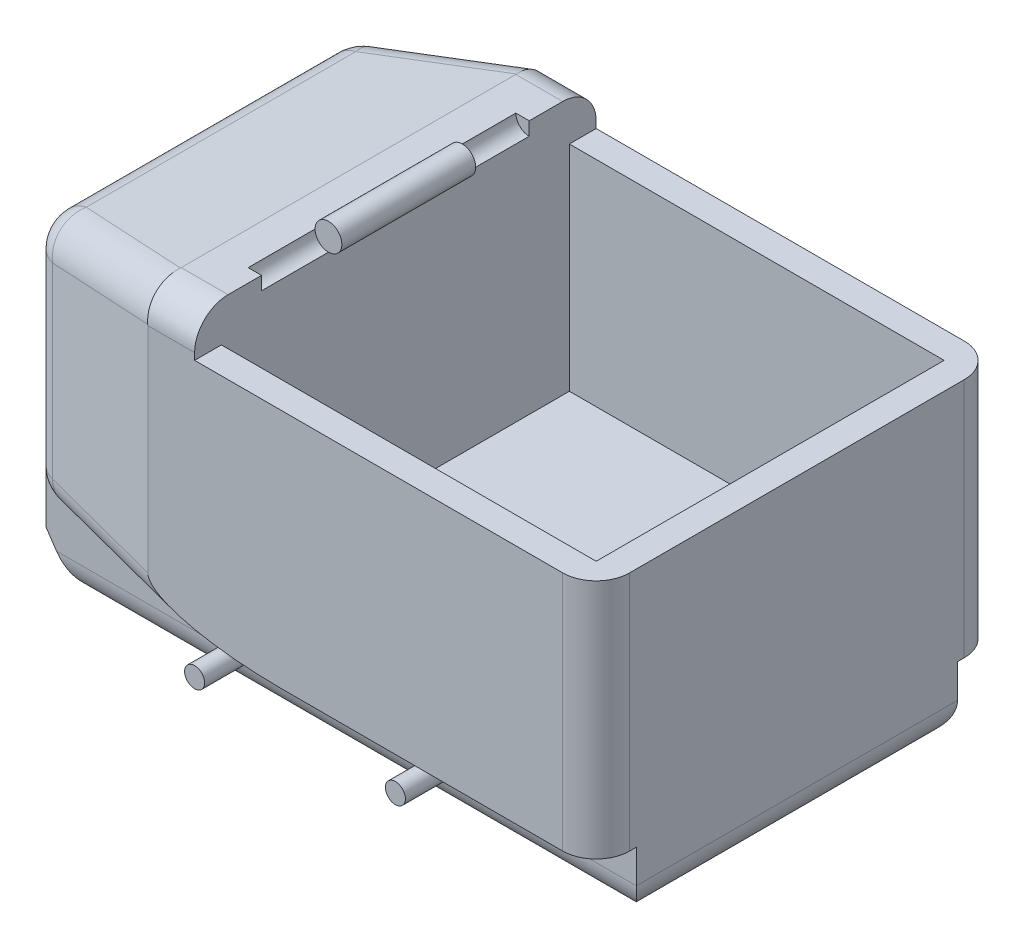
SolidWorks part; units mm, degrees
material "ABS"
ref_plane "Спереди" through (0, 0, 0) normal (0, 0, 1) x (1, 0, 0)
ref_plane "Сверху" through (0, 0, 0) normal (0, 1, 0) x (1, 0, 0)
ref_plane "Справа" through (0, 0, 0) normal (1, 0, 0) x (0, 0, -1)
sketch "Sketch1" plane through (0, 0, 0) normal (0, 1, 0) x (1, 0, 0)
  line L1 (0, 0) -> (900, 0)
  line L2 (0, 0) -> (0, 600)
  line L3 (0, 600) -> (900, 600)
  line L4 (900, 0) -> (900, 600)
  dimension "D1" = 600
  dimension "D2" = 900
extrude "Boss-Extrude1" add sketch "Sketch1" along normal blind 420
sketch "Sketch2" plane through (0, 0, 0) normal (0, -1, 0) x (1, 0, 0)
  line L0 (0, -600) -> (0, 0) construction
  line L2 (0, -60) -> (0, -540)
  line L5 (900, 0) -> (900, -600) construction
  line L6 (0, -60) -> (900, -60)
  line L8 (0, -540) -> (900, -540)
  line L9 (900, -60) -> (900, -540)
  line L12 (0, 0) -> (900, 0) construction
  line L13 (900, -600) -> (0, -600) construction
  dimension "D3" = 60
  dimension "D4" = 60
extrude "Boss-Extrude2" add sketch "Sketch2" along normal blind 100
sketch "Sketch3" plane through (0, 0, 0) normal (0, 0, 1) x (1, 0, 0)
  line L1 (900, 420) -> (300, 420)
  line L2 (900, 420) -> (900, 360)
  line L3 (900, 360) -> (300, 360)
  line L4 (300, 420) -> (300, 360)
  dimension "D1" = 60
  dimension "D2" = 600
extrude "Cut-Extrude1" cut sketch "Sketch3" against normal through all
sketch "Sketch4" plane through (0, 360, 0) normal (0, 1, 0) x (1, 0, 0)
  line L0 (900, 600) -> (900, 0) construction
  line L1 (300, 560) -> (860, 560)
  line L2 (300, 560) -> (300, 40)
  line L3 (300, 40) -> (860, 40)
  line L4 (860, 560) -> (860, 40)
  line L5 (300, 600) -> (300, 0) construction
  line L6 (300, 600) -> (900, 600) construction
  line L7 (300, 0) -> (900, 0) construction
  dimension "D1" = 40
  dimension "D2" = 40
  dimension "D3" = 40
extrude "Cut-Extrude2" cut sketch "Sketch4" against normal blind 320
sketch "Sketch5" plane through (0, 0, 0) normal (0, 0, 1) x (1, 0, 0)
  line L0 (230, 420) -> (0, 370)
  line L1 (0, 420) -> (300, 420) construction
  line L2 (0, 420) -> (0, 0) construction
  line L3 (0, 370) -> (0, 420)
  line L4 (0, 420) -> (230, 420)
  line L5 (300, 420) -> (300, 360) construction
  dimension "D1" = 70
  dimension "D2" = 50
extrude "Cut-Extrude3" cut sketch "Sketch5" against normal up to next
sketch "Sketch6" plane through (0, 0, 0) normal (0, -1, 0) x (1, 0, 0)
  line L0 (0, -60) -> (230, 0)
  line L1 (0, 0) -> (900, 0) construction
  line L2 (230, 0) -> (0, 0)
  line L3 (0, 0) -> (0, -60)
  line L4 (0, -300) -> (900, -300) construction
  line L5 (0, -60) -> (0, -540) construction
  line L6 (900, -540) -> (900, -60) construction
  line L7 (230, -600) -> (0, -600)
  line L8 (0, -600) -> (0, -540)
  line L9 (0, -540) -> (230, -600)
  line L10 (900, -60) -> (0, -60) construction
  line L11 (0, -60) -> (0, 0) construction
extrude "Cut-Extrude4" cut sketch "Sketch6" against normal through all
sketch "Sketch8" plane through (0, 0, -60) normal (0, 0, 1) x (1, 0, 0)
  line L0 (0, 0) -> (0, -100)
  line L1 (0, -100) -> (67, -100)
  line L2 (900, -100) -> (0, -100) construction
  line L3 (67, -100) -> (0, 0)
  dimension "D1" = 67
extrude "Cut-Extrude6" cut sketch "Sketch8" against normal through all
sketch "Sketch9" plane through (0, 0, -60) normal (0, 0, 1) x (1, 0, 0)
  line L0 (0, 0) -> (300, 0) construction
  line L1 (230, 0) -> (900, 0) construction
  line L2 (300, 0) -> (600, 0) construction
  line L3 (900, 0) -> (0, 0) construction
  line L4 (600, 0) -> (900, 0) construction
  circle A0 centre (300, -50) radius 15
  circle A1 centre (600, -50) radius 15
  dimension "D1" = 30
  dimension "D2" = 30
  dimension "D3" = 50
  dimension "D4" = 50
extrude "Boss-Extrude3" add sketch "Sketch9" along normal blind 60
ref_plane "Plane1" through (0, 0, -300) normal (0, 0, 1) x (1, 0, 0)
mirror "Mirror1" about plane through (0, 0, -300) normal (0, 0, 1) of "Boss-Extrude3"
sketch "Sketch10" plane through (0, 0, -300) normal (0, 0, 1) x (1, 0, 0)
  circle A0 centre (300, 420) radius 20
  dimension "D1" = 40
extrude "Boss-Extrude4" add sketch "Sketch10" along normal blind 100 and the other way blind 100
extrude "Cut-Extrude7" cut sketch "Sketch10<2>" against normal blind 100 from surface starting at face at (301.3807, 421.3807, -400)
sketch "Sketch10<2>" plane through (0, 0, -300) normal (0, 0, 1) x (1, 0, 0) same geometry as "Sketch10"
extrude "Cut-Extrude8" cut sketch "Sketch10<3>" along normal blind 100 from surface starting at face at (301.3807, 421.3807, -200)
sketch "Sketch10<3>" plane through (0, 0, -300) normal (0, 0, 1) x (1, 0, 0) same geometry as "Sketch10"
fillet "Fillet1" radius 50 12 edges at (0, 370, -300) (0, 185, -60) (0, 0, -300) (0, 185, -540) (67, -100, -300) (483.5, -100, -60) (483.5, -100, -540) (115, 395, -570) (115, 395, -30) (900, 180, 0) (900, -100, -300) (900, 180, -600)
fillet "Fillet2" radius 50 4 edges at (27.2876, 0, -545.9139) (133.6895, 0, -574.8755) (27.2876, 0, -54.0861) (133.6895, 0, -25.1245)
fillet "Fillet3" radius 50 2 edges at (294.5375, 420, -600) (294.5375, 420, 0)
